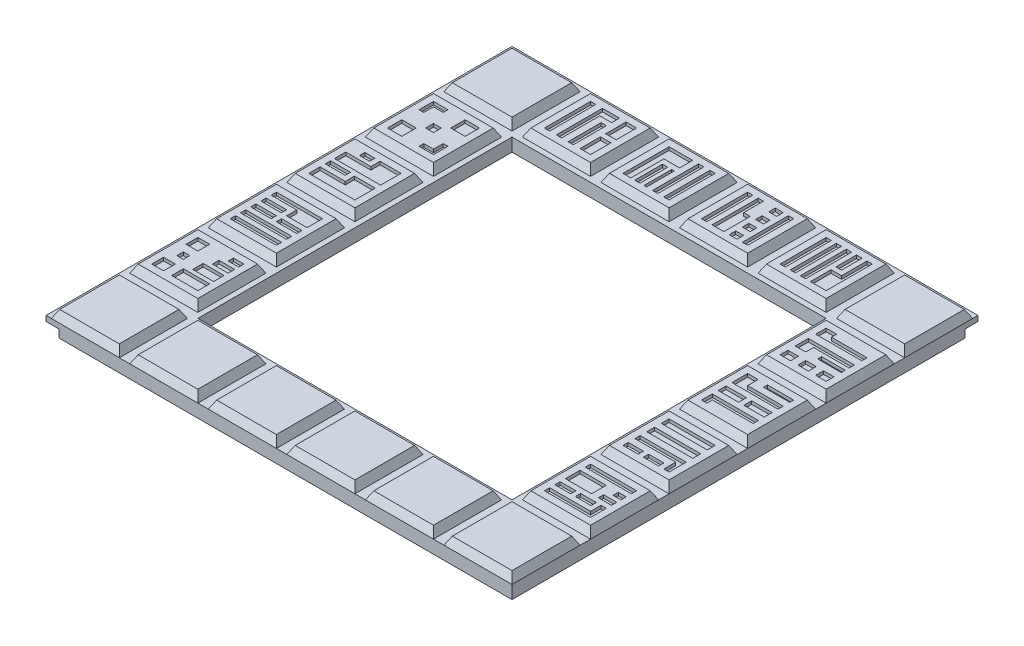
SolidWorks part; units mm, degrees
ref_plane "Front Plane" through (0, 0, 0) normal (0, 0, 1) x (1, 0, 0)
ref_plane "Top Plane" through (0, 0, 0) normal (0, 1, 0) x (1, 0, 0)
ref_plane "Right Plane" through (0, 0, 0) normal (1, 0, 0) x (0, 0, -1)
sketch "Sketch1" plane through (0, 0, 0) normal (0, 1, 0) x (1, 0, 0)
  line L1 (0, 0) -> (-180, 0)
  line L2 (0, 0) -> (0, 180)
  line L3 (0, 180) -> (-180, 180)
  line L4 (-180, 0) -> (-180, 180)
  dimension "D1" = 180
  dimension "D2" = 180
extrude "Boss-Extrude1" add sketch "Sketch1" along normal blind 5
sketch "Sketch2" plane through (0, 5, 0) normal (0, 1, 0) x (1, 0, 0)
  line L0 (-180, 180) -> (-180, 0) construction
  line L1 (-150, 150) -> (-30, 150)
  line L2 (-150, 150) -> (-150, 30)
  line L3 (-150, 30) -> (-30, 30)
  line L4 (-30, 150) -> (-30, 30)
  line L5 (0, 180) -> (-180, 180) construction
  dimension "D1" = 120
  dimension "D2" = 120
  dimension "D3" = 30
  dimension "D4" = 30
extrude "Cut-Extrude1" cut sketch "Sketch2" against normal through all
sketch "Sketch3" plane through (0, 5, 0) normal (0, 1, 0) x (1, 0, 0)
  line L0 (-180, 180) -> (-180, 0) construction
  line L1 (-178, 178) -> (-152, 178)
  line L2 (-178, 178) -> (-178, 152)
  line L3 (-178, 152) -> (-152, 152)
  line L4 (-152, 178) -> (-152, 152)
  line L5 (-148, 152) -> (-122, 152)
  line L6 (-148, 152) -> (-148, 178)
  line L7 (-148, 178) -> (-122, 178)
  line L8 (-122, 152) -> (-122, 178)
  line L9 (-118, 178) -> (-92, 178)
  line L10 (-118, 178) -> (-118, 152)
  line L11 (-118, 152) -> (-92, 152)
  line L12 (-92, 178) -> (-92, 152)
  line L13 (-88, 152) -> (-62, 152)
  line L14 (-88, 152) -> (-88, 178)
  line L15 (-88, 178) -> (-62, 178)
  line L16 (-62, 152) -> (-62, 178)
  line L17 (-58, 178) -> (-32, 178)
  line L18 (-58, 178) -> (-58, 152)
  line L19 (-58, 152) -> (-32, 152)
  line L20 (-32, 178) -> (-32, 152)
  line L21 (-28, 152) -> (-2, 152)
  line L22 (-28, 152) -> (-28, 178)
  line L23 (-28, 178) -> (-2, 178)
  line L24 (-2, 152) -> (-2, 178)
  line L25 (-28, 148) -> (-2, 148)
  line L26 (-28, 148) -> (-28, 122)
  line L27 (-28, 122) -> (-2, 122)
  line L28 (-2, 148) -> (-2, 122)
  line L29 (-2, 118) -> (-28, 118)
  line L30 (-2, 118) -> (-2, 92)
  line L31 (-2, 92) -> (-28, 92)
  line L32 (-28, 118) -> (-28, 92)
  line L33 (-28, 88) -> (-2, 88)
  line L34 (-28, 88) -> (-28, 62)
  line L35 (-28, 62) -> (-2, 62)
  line L36 (-2, 88) -> (-2, 62)
  line L37 (-28, 58) -> (-2, 58)
  line L38 (-28, 58) -> (-28, 32)
  line L39 (-28, 32) -> (-2, 32)
  line L40 (-2, 58) -> (-2, 32)
  line L41 (-28, 28) -> (-2, 28)
  line L42 (-28, 28) -> (-28, 2)
  line L43 (-28, 2) -> (-2, 2)
  line L44 (-2, 28) -> (-2, 2)
  line L45 (-32, 28) -> (-58, 28)
  line L46 (-32, 28) -> (-32, 2)
  line L47 (-32, 2) -> (-58, 2)
  line L48 (-58, 28) -> (-58, 2)
  line L49 (-62, 28) -> (-88, 28)
  line L50 (-62, 28) -> (-62, 2)
  line L51 (-62, 2) -> (-88, 2)
  line L52 (-88, 28) -> (-88, 2)
  line L53 (-92, 28) -> (-118, 28)
  line L54 (-92, 28) -> (-92, 2)
  line L55 (-92, 2) -> (-118, 2)
  line L56 (-118, 28) -> (-118, 2)
  line L57 (-122, 28) -> (-148, 28)
  line L58 (-122, 28) -> (-122, 2)
  line L59 (-122, 2) -> (-148, 2)
  line L60 (-148, 28) -> (-148, 2)
  line L61 (-152, 28) -> (-178, 28)
  line L62 (-152, 28) -> (-152, 2)
  line L63 (-152, 2) -> (-178, 2)
  line L64 (-178, 28) -> (-178, 2)
  line L65 (-178, 32) -> (-152, 32)
  line L66 (-178, 32) -> (-178, 58)
  line L67 (-178, 58) -> (-152, 58)
  line L68 (-152, 32) -> (-152, 58)
  line L69 (-178, 62) -> (-152, 62)
  line L70 (-178, 62) -> (-178, 88)
  line L71 (-178, 88) -> (-152, 88)
  line L72 (-152, 62) -> (-152, 88)
  line L73 (-178, 92) -> (-152, 92)
  line L74 (-178, 92) -> (-178, 118)
  line L75 (-178, 118) -> (-152, 118)
  line L76 (-152, 92) -> (-152, 118)
  line L77 (-178, 122) -> (-152, 122)
  line L78 (-178, 122) -> (-178, 148)
  line L79 (-178, 148) -> (-152, 148)
  line L80 (-152, 122) -> (-152, 148)
  line L81 (0, 180) -> (-180, 180) construction
  line L82 (-180, 0) -> (0, 0) construction
  line L83 (0, 0) -> (0, 180) construction
  dimension "D1" = 26
  dimension "D2" = 2
  dimension "D3" = 2
  dimension "D4" = 4
  dimension "D5" = 2
  dimension "D6" = 4
  dimension "D7" = 4
  dimension "D8" = 4
  dimension "D9" = 4
  dimension "D10" = 4
  dimension "D11" = 2
  dimension "D12" = 4
  dimension "D13" = 4
extrude "Boss-Extrude2" add sketch "Sketch3" along normal blind 3
chamfer "Chamfer1" distance 3 distance2 1.6 80 edges at (-15, 8, -178) (-2, 8, -165) (-15, 8, -152) (-28, 8, -165) (-105, 8, -2) (-118, 8, -15) (-105, 8, -28) (-92, 8, -15) (-135, 8, -2) (-148, 8, -15) (-135, 8, -28) (-122, 8, -15) (-165, 8, -2) (-178, 8, -15) (-165, 8, -28) (-152, 8, -15) (-165, 8, -58) (-152, 8, -45) (-165, 8, -32) (-178, 8, -45) (-165, 8, -88) (-152, 8, -75) (-165, 8, -62) (-178, 8, -75) (-165, 8, -118) (-152, 8, -105) (-165, 8, -92) (-178, 8, -105) (-15, 8, -58) (-2, 8, -45) (-15, 8, -32) (-28, 8, -45) (-75, 8, -2) (-88, 8, -15) (-75, 8, -28) (-62, 8, -15) (-45, 8, -2) (-58, 8, -15) (-45, 8, -28) (-32, 8, -15) (-15, 8, -28) (-2, 8, -15) (-15, 8, -2) (-28, 8, -15) (-15, 8, -88) (-2, 8, -75) (-15, 8, -62) (-28, 8, -75) (-15, 8, -92) (-28, 8, -105) (-15, 8, -118) (-2, 8, -105) (-15, 8, -148) (-2, 8, -135) (-15, 8, -122) (-28, 8, -135) (-75, 8, -178) (-62, 8, -165) (-75, 8, -152) (-88, 8, -165) (-105, 8, -178) (-92, 8, -165) (-105, 8, -152) (-118, 8, -165) (-135, 8, -178) (-122, 8, -165) (-135, 8, -152) (-148, 8, -165) (-165, 8, -148) (-152, 8, -135) (-165, 8, -122) (-178, 8, -135) (-165, 8, -178) (-152, 8, -165) (-165, 8, -152) (-178, 8, -165) (-45, 8, -178) (-32, 8, -165) (-45, 8, -152) (-58, 8, -165)
sketch "Sketch4" plane through (0, 8, 0) normal (0, 1, 0) x (1, 0, 0)
  line L0 (-123.6, 176.4) -> (-146.4, 176.4) construction
  line L1 (-143.8, 173.8) -> (-141.8, 173.8)
  line L2 (-143.8, 173.8) -> (-143.8, 156.2)
  line L3 (-143.8, 156.2) -> (-141.8, 156.2)
  line L4 (-141.8, 173.8) -> (-141.8, 156.2)
  line L5 (-139.25, 156.2) -> (-137.25, 156.2)
  line L6 (-139.25, 156.2) -> (-139.25, 173.8)
  line L7 (-139.25, 173.8) -> (-137.25, 173.8)
  line L8 (-137.25, 156.2) -> (-137.25, 173.8)
  line L9 (-137.25, 173.8) -> (-132.75, 173.8)
  line L10 (-146.4, 153.6) -> (-123.6, 153.6) construction
  line L11 (-137.25, 170.8) -> (-132.75, 170.8)
  line L12 (-132.75, 173.8) -> (-132.75, 170.8)
  line L13 (-132.75, 168.8) -> (-134.75, 168.8)
  line L14 (-132.75, 168.8) -> (-132.75, 156.2)
  line L15 (-132.75, 156.2) -> (-134.75, 156.2)
  line L16 (-134.75, 168.8) -> (-134.75, 156.2)
  line L17 (-130.2, 156.2) -> (-126.2, 156.2)
  line L18 (-130.2, 156.2) -> (-130.2, 164)
  line L19 (-130.2, 164) -> (-126.2, 164)
  line L20 (-126.2, 156.2) -> (-126.2, 164)
  line L21 (-130.2, 166) -> (-126.2, 166)
  line L22 (-130.2, 166) -> (-130.2, 173.8)
  line L23 (-130.2, 173.8) -> (-126.2, 173.8)
  line L24 (-126.2, 166) -> (-126.2, 173.8)
  line L25 (-113.8, 156.2) -> (-110.8, 156.2)
  line L26 (-113.8, 156.2) -> (-113.8, 173.8)
  line L27 (-113.8, 173.8) -> (-110.8, 173.8)
  line L28 (-110.8, 156.2) -> (-110.8, 173.8)
  line L29 (-110.8, 168.8) -> (-104.8, 168.8)
  line L30 (-146.4, 176.4) -> (-146.4, 153.6) construction
  line L31 (-110.8, 173.8) -> (-104.8, 173.8)
  line L32 (-104.8, 168.8) -> (-104.8, 173.8)
  line L33 (-109.3, 166.8) -> (-107.3, 166.8)
  line L34 (-109.3, 166.8) -> (-109.3, 156.2)
  line L35 (-109.3, 156.2) -> (-107.3, 156.2)
  line L36 (-107.3, 166.8) -> (-107.3, 156.2)
  line L37 (-105.8, 156.2) -> (-104.8, 156.2)
  line L38 (-105.8, 156.2) -> (-105.8, 166.8)
  line L39 (-105.8, 166.8) -> (-104.8, 166.8)
  line L40 (-104.8, 156.2) -> (-104.8, 166.8)
  line L41 (-102.5, 173.8) -> (-100.5, 173.8)
  line L42 (-102.5, 173.8) -> (-102.5, 156.2)
  line L43 (-102.5, 156.2) -> (-100.5, 156.2)
  line L44 (-100.5, 173.8) -> (-100.5, 156.2)
  line L45 (-98.2, 156.2) -> (-96.2, 156.2)
  line L46 (-98.2, 156.2) -> (-98.2, 173.8)
  line L47 (-98.2, 173.8) -> (-96.2, 173.8)
  line L48 (-96.2, 156.2) -> (-96.2, 173.8)
  line L49 (-83.8, 173.8) -> (-81.8, 173.8)
  line L50 (-83.8, 173.8) -> (-83.8, 156.2)
  line L51 (-83.8, 156.2) -> (-81.8, 156.2)
  line L52 (-81.8, 173.8) -> (-81.8, 156.2)
  line L53 (-79.7667, 156.2) -> (-77.7667, 156.2)
  line L54 (-79.7667, 156.2) -> (-79.7667, 173.8)
  line L55 (-79.7667, 173.8) -> (-77.7667, 173.8)
  line L56 (-77.7667, 156.2) -> (-77.7667, 173.8)
  line L57 (-77.7667, 166.2667) -> (-75.2667, 166.2667)
  line L58 (-123.6, 153.6) -> (-123.6, 176.4) construction
  line L59 (-77.7667, 156.2) -> (-75.2667, 156.2)
  line L60 (-75.2667, 166.2667) -> (-75.2667, 156.2)
  line L61 (-73.2333, 156.2) -> (-70.2333, 156.2)
  line L62 (-73.2333, 156.2) -> (-73.2333, 158.7)
  line L63 (-73.2333, 158.7) -> (-70.2333, 158.7)
  line L64 (-70.2333, 156.2) -> (-70.2333, 158.7)
  line L65 (-73.2333, 161.2333) -> (-70.2333, 161.2333)
  line L66 (-73.2333, 161.2333) -> (-73.2333, 163.7333)
  line L67 (-73.2333, 163.7333) -> (-70.2333, 163.7333)
  line L68 (-70.2333, 161.2333) -> (-70.2333, 163.7333)
  line L69 (-73.2333, 166.2667) -> (-70.2333, 166.2667)
  line L70 (-73.2333, 166.2667) -> (-73.2333, 168.7667)
  line L71 (-73.2333, 168.7667) -> (-70.2333, 168.7667)
  line L72 (-70.2333, 166.2667) -> (-70.2333, 168.7667)
  line L73 (-73.2333, 171.3) -> (-70.2333, 171.3)
  line L74 (-73.2333, 171.3) -> (-73.2333, 173.8)
  line L75 (-73.2333, 173.8) -> (-70.2333, 173.8)
  line L76 (-70.2333, 171.3) -> (-70.2333, 173.8)
  line L77 (-68.2, 173.8) -> (-66.2, 173.8)
  line L78 (-68.2, 173.8) -> (-68.2, 156.2)
  line L79 (-68.2, 156.2) -> (-66.2, 156.2)
  line L80 (-66.2, 173.8) -> (-66.2, 156.2)
  line L81 (-53.8, 173.8) -> (-51.8, 173.8)
  line L82 (-53.8, 173.8) -> (-53.8, 156.2)
  line L83 (-53.8, 156.2) -> (-51.8, 156.2)
  line L84 (-51.8, 173.8) -> (-51.8, 156.2)
  line L85 (-49.9333, 156.2) -> (-47.9333, 156.2)
  line L86 (-49.9333, 156.2) -> (-49.9333, 173.8)
  line L87 (-49.9333, 173.8) -> (-47.9333, 173.8)
  line L88 (-47.9333, 156.2) -> (-47.9333, 173.8)
  line L89 (-46.0667, 173.8) -> (-44.0667, 173.8)
  line L90 (-46.0667, 173.8) -> (-46.0667, 156.2)
  line L91 (-46.0667, 156.2) -> (-44.0667, 156.2)
  line L92 (-44.0667, 173.8) -> (-44.0667, 156.2)
  line L93 (-42.2, 173.8) -> (-40.0667, 173.8)
  line L94 (-42.2, 173.8) -> (-42.2, 165.9333)
  line L95 (-42.2, 165.9333) -> (-40.0667, 165.9333)
  line L96 (-40.0667, 173.8) -> (-40.0667, 165.9333)
  line L97 (-38.2, 173.8) -> (-36.2, 173.8)
  line L98 (-38.2, 173.8) -> (-38.2, 156.2)
  line L99 (-38.2, 156.2) -> (-36.2, 156.2)
  line L100 (-36.2, 173.8) -> (-36.2, 156.2)
  line L101 (-42.2, 156.2) -> (-38.2, 156.2)
  line L102 (-42.2, 156.2) -> (-42.2, 164.0667)
  line L103 (-42.2, 164.0667) -> (-38.2, 164.0667)
  line L104 (-93.6, 153.6) -> (-93.6, 176.4) construction
  line L105 (-116.4, 176.4) -> (-116.4, 153.6) construction
  line L106 (-63.6, 153.6) -> (-63.6, 176.4) construction
  line L107 (-86.4, 176.4) -> (-86.4, 153.6) construction
  line L108 (-56.4, 176.4) -> (-56.4, 153.6) construction
  line L109 (-33.6, 153.6) -> (-33.6, 176.4) construction
  line L110 (-70.2333, 171.3) -> (-70.2333, 168.7667) construction
  line L111 (-70.2333, 166.2667) -> (-70.2333, 163.7333) construction
  line L112 (-70.2333, 161.2333) -> (-70.2333, 158.7) construction
  line L113 (-141.8, 156.2) -> (-139.25, 156.2) construction
  line L114 (-132.75, 156.2) -> (-130.2, 156.2) construction
  line L115 (-104.8, 156.2) -> (-102.5, 156.2) construction
  line L116 (-100.5, 156.2) -> (-98.2, 156.2) construction
  line L117 (-51.8, 156.2) -> (-49.9333, 156.2) construction
  line L118 (-47.9333, 156.2) -> (-46.0667, 156.2) construction
  line L119 (-44.0667, 156.2) -> (-42.2, 156.2) construction
  line L120 (-42.2, 164.0667) -> (-42.2, 165.9333) construction
  line L121 (-40.0667, 173.8) -> (-38.2, 173.8) construction
  line L122 (-81.8, 156.2) -> (-79.7667, 156.2) construction
  line L123 (-75.2667, 156.2) -> (-73.2333, 156.2) construction
  line L124 (-70.2333, 156.2) -> (-68.2, 156.2) construction
  point P120 (-127.7927, 145.733)
  dimension "D1" = 2.6
  dimension "D2" = 2.6
  dimension "D3" = 2.6
  dimension "D4" = 2.6
  dimension "D5" = 2.6
  dimension "D6" = 2
  dimension "D7" = 2
  dimension "D8" = 2
  dimension "D9" = 1
  dimension "D10" = 2
  dimension "D11" = 2
  dimension "D12" = 2.6
  dimension "D13" = 2.6
  dimension "D14" = 2.6
  dimension "D15" = 2.6
  dimension "D16" = 2
  dimension "D17" = 2
  dimension "D18" = 2.5
  dimension "D19" = 2
  dimension "D21" = 3
  dimension "D23" = 2.6
  dimension "D24" = 2.6
  dimension "D25" = 2
  dimension "D26" = 2.5
  dimension "D27" = 2
  dimension "D28" = 3
  dimension "D29" = 2
  dimension "D30" = 2
  dimension "D31" = 4
  dimension "D32" = 4
  dimension "D33" = 3
  dimension "D34" = 6
  dimension "D35" = 1.5
  dimension "D36" = 5
  dimension "D37" = 2
  dimension "D38" = 2
  dimension "D39" = 2
  dimension "D40" = 2.5
  dimension "D41" = 2
  dimension "D42" = 2
  dimension "D43" = 4
extrude "Motifs_Ligne_1" cut sketch "Sketch4" against normal blind 1.2 contours L13 L16 L15 L14 | L12 L9 L8 L11 | L17 L20 L19 L18 | L21 L24 L23 L22 | L5 L8 L7 L6 | L25 L28 L27 L26 | L29 L32 L31 L28 | L36 L33 L34 L35 | L37 L40 L39 L38 | L44 L41 L42 L43 | L45 L48 L47 L46 | L103 L102 L101 L98 | L100 L97 L98 L99 | L96 L93 L94 L95 | L92 L89 L90 L91 | L85 L88 L87 L86 | L84 L81 L82 L83 | L73 L76 L75 L74 | L53 L56 L55 L54 | L60 L57 L56 L59 | L52 L49 L50 L51 | L65 L68 L67 L66 | L61 L64 L63 L62 | L69 L72 L71 L70 | L80 L77 L78 L79 | L2 L3 L4 L1
sketch "Sketch5" plane through (0, 0, 0) normal (0, -1, 0) x (1, 0, 0)
  line L0 (0, -175) -> (0, -180)
  line L1 (-180, -180) -> (-180, 0)
  line L2 (-180, 0) -> (-175, 0)
  line L4 (-175, -175) -> (0, -175)
  line L5 (0, -180) -> (-180, -180)
  line L6 (-175, 0) -> (-175, -175)
  line L7 (-180, 0) -> (0, 0) construction
  dimension "D1" = 5
  dimension "D2" = 5
  dimension "D3" = 0
  dimension "D4" = 0
extrude "Cut-Extrude3" cut sketch "Sketch5" against normal blind 3
sketch "Sketch6" plane through (0, 0, 0) normal (0, -1, 0) x (1, 0, 0)
  line L0 (0, 0) -> (0, -194.7494)
  line L1 (0, -194.7494) -> (-2, -194.7494)
  line L2 (-2, -194.7494) -> (-2, -2)
  line L3 (-2, -2) -> (-190.0347, -2)
  line L4 (-190.0347, -2) -> (-190.0347, 0)
  line L5 (-190.0347, 0) -> (0, 0)
  dimension "D1" = 2
  dimension "D2" = 2
extrude "Cut-Extrude4" cut sketch "Sketch6" against normal through all
sketch "Sketch7" plane through (0, 8, 0) normal (0, 1, 0) x (1, 0, 0)
  line L0 (-173.8, 146.4) -> (-173.8, 33.6) construction
  line L1 (-153.6, 146.4) -> (-176.4, 146.4) construction
  line L2 (-176.4, 33.6) -> (-153.6, 33.6) construction
  line L3 (-156.2, 146.4) -> (-156.2, 33.6) construction
  line L4 (-176.4, 36.2) -> (-153.6, 36.2) construction
  line L5 (-176.4, 56.4) -> (-176.4, 33.6) construction
  line L6 (-153.6, 33.6) -> (-153.6, 56.4) construction
  line L7 (-176.4, 143.8) -> (-153.6, 143.8) construction
  line L8 (-176.4, 146.4) -> (-176.4, 123.6) construction
  line L9 (-153.6, 123.6) -> (-153.6, 146.4) construction
  line L10 (-176.4, 126.2) -> (-153.6, 126.2) construction
  line L11 (-176.4, 96.2) -> (-153.6, 96.2) construction
  line L12 (-176.4, 116.4) -> (-176.4, 93.6) construction
  line L13 (-153.6, 93.6) -> (-153.6, 116.4) construction
  line L14 (-176.4, 113.8) -> (-153.6, 113.8) construction
  line L15 (-176.4, 83.8) -> (-153.6, 83.8) construction
  line L16 (-176.4, 86.4) -> (-176.4, 63.6) construction
  line L17 (-153.6, 63.6) -> (-153.6, 86.4) construction
  line L18 (-153.6, 66.2) -> (-176.4, 66.2) construction
  line L19 (-176.4, 53.8) -> (-153.6, 53.8) construction
  line L20 (-176.4, 123.6) -> (-153.6, 123.6) construction
  line L21 (-153.6, 116.4) -> (-176.4, 116.4) construction
  line L22 (-176.4, 93.6) -> (-153.6, 93.6) construction
  line L23 (-153.6, 86.4) -> (-176.4, 86.4) construction
  line L24 (-176.4, 63.6) -> (-153.6, 63.6) construction
  line L25 (-153.6, 56.4) -> (-176.4, 56.4) construction
  line L26 (-173.8, 138.3) -> (-172, 138.3)
  line L27 (-173.8, 126.2) -> (-168.3, 126.2)
  line L28 (-173.8, 126.2) -> (-173.8, 131.7)
  line L29 (-173.8, 131.7) -> (-168.3, 131.7)
  line L30 (-168.3, 126.2) -> (-168.3, 131.7)
  line L31 (-166.5, 133.5) -> (-163.5, 133.5)
  line L32 (-166.5, 133.5) -> (-166.5, 136.5)
  line L33 (-166.5, 136.5) -> (-163.5, 136.5)
  line L34 (-163.5, 133.5) -> (-163.5, 136.5)
  line L35 (-156.2, 143.8) -> (-161.7, 143.8)
  line L36 (-156.2, 143.8) -> (-156.2, 138.3)
  line L37 (-156.2, 138.3) -> (-161.7, 138.3)
  line L38 (-161.7, 143.8) -> (-161.7, 138.3)
  line L39 (-172, 138.3) -> (-172, 142)
  line L40 (-172, 142) -> (-168.3, 142)
  line L41 (-168.3, 142) -> (-168.3, 143.8)
  line L42 (-168.3, 143.8) -> (-173.8, 143.8)
  line L43 (-173.8, 143.8) -> (-173.8, 138.3)
  line L44 (-161.7, 126.2) -> (-156.2, 126.2)
  line L45 (-156.2, 126.2) -> (-156.2, 131.7)
  line L46 (-156.2, 131.7) -> (-158, 131.7)
  line L47 (-158, 131.7) -> (-158, 128)
  line L48 (-158, 128) -> (-161.7, 128)
  line L49 (-161.7, 126.2) -> (-161.7, 128)
  line L50 (-173.8, 131.7) -> (-173.8, 138.3) construction
  line L51 (-168.3, 143.8) -> (-161.7, 143.8) construction
  line L52 (-168.3, 126.2) -> (-161.7, 126.2) construction
  line L53 (-156.2, 131.7) -> (-156.2, 138.3) construction
  line L54 (-172, 138.3) -> (-172, 131.7) construction
  line L55 (-166.5, 133.5) -> (-173.8, 133.5) construction
  line L56 (-166.5, 133.5) -> (-166.5, 126.2) construction
  line L57 (-163.5, 136.5) -> (-163.5, 143.8) construction
  line L58 (-163.5, 136.5) -> (-156.2, 136.5) construction
  line L59 (-173.8, 106) -> (-156.2, 106)
  line L60 (-156.2, 106) -> (-156.2, 113.8)
  line L61 (-156.2, 113.8) -> (-164.2, 113.8)
  line L62 (-164.2, 113.8) -> (-164.2, 110.3)
  line L63 (-164.2, 110.3) -> (-173.8, 110.3)
  line L64 (-173.8, 110.3) -> (-173.8, 106)
  line L65 (-173.8, 96.2) -> (-173.8, 100.5)
  line L66 (-173.8, 100.5) -> (-164.2, 100.5)
  line L67 (-164.2, 100.5) -> (-164.2, 104)
  line L68 (-164.2, 104) -> (-156.2, 104)
  line L69 (-156.2, 104) -> (-156.2, 96.2)
  line L70 (-156.2, 96.2) -> (-173.8, 96.2)
  line L71 (-173.8, 83.8) -> (-156.2, 83.8)
  line L72 (-173.8, 104.5) -> (-166.2, 104.5)
  line L73 (-173.8, 104.5) -> (-173.8, 102.5)
  line L74 (-173.8, 102.5) -> (-166.2, 102.5)
  line L75 (-166.2, 104.5) -> (-166.2, 102.5)
  line L76 (-170, 113.8) -> (-166.2, 113.8)
  line L77 (-170, 113.8) -> (-170, 111.8)
  line L78 (-170, 111.8) -> (-166.2, 111.8)
  line L79 (-166.2, 113.8) -> (-166.2, 111.8)
  line L80 (-173.8, 66.2) -> (-156.2, 66.2)
  line L81 (-173.8, 66.2) -> (-173.8, 68.2)
  line L82 (-173.8, 68.2) -> (-156.2, 68.2)
  line L83 (-156.2, 66.2) -> (-156.2, 68.2)
  line L84 (-156.2, 70.1) -> (-173.8, 70.1)
  line L85 (-156.2, 70.1) -> (-156.2, 72.1)
  line L86 (-156.2, 72.1) -> (-173.8, 72.1)
  line L87 (-173.8, 70.1) -> (-173.8, 72.1)
  line L88 (-173.8, 74) -> (-166, 74)
  line L89 (-173.8, 74) -> (-173.8, 76)
  line L90 (-173.8, 76) -> (-166, 76)
  line L91 (-166, 74) -> (-166, 76)
  line L92 (-164, 76) -> (-156.2, 76)
  line L93 (-164, 76) -> (-164, 74)
  line L94 (-164, 74) -> (-156.2, 74)
  line L95 (-156.2, 76) -> (-156.2, 74)
  line L96 (-173.8, 77.9) -> (-166, 77.9)
  line L97 (-173.8, 77.9) -> (-173.8, 79.9)
  line L98 (-173.8, 79.9) -> (-166, 79.9)
  line L99 (-166, 77.9) -> (-166, 79.9)
  line L100 (-156.2, 83.8) -> (-156.2, 77.9)
  line L101 (-156.2, 77.9) -> (-164, 77.9)
  line L102 (-164, 77.9) -> (-164, 81.8)
  line L103 (-164, 81.8) -> (-173.8, 81.8)
  line L104 (-173.8, 81.8) -> (-173.8, 83.8)
  line L105 (-173.8, 68.2) -> (-173.8, 70.1) construction
  line L106 (-173.8, 72.1) -> (-173.8, 74) construction
  line L107 (-166, 79.9) -> (-166, 81.8) construction
  line L108 (-166, 77.9) -> (-166, 76) construction
  line L109 (-166, 74) -> (-166, 72.1) construction
  line L110 (-166, 70.1) -> (-166, 68.2) construction
  line L111 (-159.5704, 40.7) -> (-159.5704, 42.2333) construction
  line L112 (-173.8, 53.8) -> (-169.3, 53.8)
  line L113 (-173.8, 53.8) -> (-173.8, 49.3)
  line L114 (-173.8, 49.3) -> (-169.3, 49.3)
  line L115 (-169.3, 53.8) -> (-169.3, 49.3)
  line L116 (-173.8, 36.2) -> (-169.3, 36.2)
  line L117 (-173.8, 36.2) -> (-173.8, 40.7)
  line L118 (-173.8, 40.7) -> (-169.3, 40.7)
  line L119 (-169.3, 36.2) -> (-169.3, 40.7)
  line L120 (-169.3, 43.75) -> (-171.8, 43.75)
  line L121 (-169.3, 43.75) -> (-169.3, 46.25)
  line L122 (-169.3, 46.25) -> (-171.8, 46.25)
  line L123 (-171.8, 43.75) -> (-171.8, 46.25)
  line L124 (-156.2, 53.8) -> (-160.2, 53.8)
  line L125 (-156.2, 53.8) -> (-156.2, 51.8)
  line L126 (-156.2, 51.8) -> (-160.2, 51.8)
  line L127 (-160.2, 53.8) -> (-160.2, 51.8)
  line L128 (-156.2, 50.2667) -> (-162.2, 50.2667)
  line L129 (-156.2, 50.2667) -> (-156.2, 47.7667)
  line L130 (-156.2, 47.7667) -> (-162.2, 47.7667)
  line L131 (-162.2, 50.2667) -> (-162.2, 47.7667)
  line L132 (-156.2, 46.2333) -> (-164.2, 46.2333)
  line L133 (-156.2, 46.2333) -> (-156.2, 42.2333)
  line L134 (-156.2, 42.2333) -> (-164.2, 42.2333)
  line L135 (-164.2, 46.2333) -> (-164.2, 42.2333)
  line L136 (-156.2, 40.7) -> (-166.2, 40.7)
  line L137 (-156.2, 40.7) -> (-156.2, 36.2)
  line L138 (-156.2, 36.2) -> (-166.2, 36.2)
  line L139 (-166.2, 40.7) -> (-166.2, 36.2)
  line L140 (-159.5704, 46.2333) -> (-159.5704, 47.7667) construction
  line L141 (-159.5704, 50.2667) -> (-159.5704, 51.8) construction
  line L142 (-169.3, 46.25) -> (-169.3, 49.3) construction
  line L143 (-169.3, 43.75) -> (-169.3, 40.7) construction
  dimension "D1" = 2.6
  dimension "D2" = 2.6
  dimension "D3" = 2.6
  dimension "D4" = 2.6
  dimension "D5" = 2.6
  dimension "D6" = 2.6
  dimension "D7" = 2.6
  dimension "D8" = 2.6
  dimension "D9" = 2.6
  dimension "D10" = 2.6
  dimension "D11" = 1.8
  dimension "D12" = 5.5
  dimension "D13" = 1.5
  dimension "D14" = 3
  dimension "D15" = 2
  dimension "D16" = 2
  dimension "D17" = 2
  dimension "D18" = 8
  dimension "D19" = 2
  dimension "D20" = 3.8
  dimension "D21" = 2
  dimension "D22" = 2
  dimension "D23" = 2
  dimension "D24" = 2.5
  dimension "D25" = 4
  dimension "D26" = 4.5
  dimension "D27" = 10
  dimension "D28" = 8
  dimension "D29" = 6
  dimension "D30" = 4
  dimension "D31" = 2.5
  dimension "D32" = 4.5
extrude "Cut-Extrude5" cut sketch "Sketch7" against normal blind 1.2
sketch "Sketch8" plane through (0, 8, 0) normal (0, 1, 0) x (1, 0, 0)
  line L0 (-23.8, 38.2) -> (-23.8, 36.2)
  line L1 (-15.2, 133.5) -> (-6.2, 133.5)
  line L2 (-15.2, 133.5) -> (-15.2, 132)
  line L3 (-15.2, 132) -> (-6.2, 132)
  line L4 (-6.2, 133.5) -> (-6.2, 132)
  line L5 (-23.8, 129.2) -> (-19.8, 129.2)
  line L6 (-23.8, 129.2) -> (-23.8, 126.2)
  line L7 (-23.8, 126.2) -> (-19.8, 126.2)
  line L8 (-19.8, 129.2) -> (-19.8, 126.2)
  line L9 (-17, 129.2) -> (-13, 129.2)
  line L10 (-17, 129.2) -> (-17, 126.2)
  line L11 (-17, 126.2) -> (-13, 126.2)
  line L12 (-13, 129.2) -> (-13, 126.2)
  line L13 (-10.2, 129.2) -> (-6.2, 129.2)
  line L14 (-10.2, 129.2) -> (-10.2, 126.2)
  line L15 (-10.2, 126.2) -> (-6.2, 126.2)
  line L16 (-6.2, 129.2) -> (-6.2, 126.2)
  line L17 (-16.2, 113.8) -> (-6.2, 113.8)
  line L18 (-16.2, 113.8) -> (-16.2, 112.3)
  line L19 (-16.2, 112.3) -> (-6.2, 112.3)
  line L20 (-6.2, 113.8) -> (-6.2, 112.3)
  line L21 (-23.8, 105.5524) -> (-16, 105.5524)
  line L22 (-23.8, 105.5524) -> (-23.8, 102.5524)
  line L23 (-23.8, 102.5524) -> (-16, 102.5524)
  line L24 (-16, 105.5524) -> (-16, 102.5524)
  line L25 (-14, 105.5524) -> (-6.2, 105.5524)
  line L26 (-14, 105.5524) -> (-14, 102.5524)
  line L27 (-14, 102.5524) -> (-6.2, 102.5524)
  line L28 (-6.2, 105.5524) -> (-6.2, 102.5524)
  line L29 (-23.8, 83.8) -> (-6.2, 83.8)
  line L30 (-23.8, 83.8) -> (-23.8, 80.8)
  line L31 (-23.8, 80.8) -> (-6.2, 80.8)
  line L32 (-6.2, 83.8) -> (-6.2, 80.8)
  line L33 (-6.2, 78.2667) -> (-23.8, 78.2667)
  line L34 (-6.2, 78.2667) -> (-6.2, 75.2667)
  line L35 (-6.2, 75.2667) -> (-23.8, 75.2667)
  line L36 (-23.8, 78.2667) -> (-23.8, 75.2667)
  line L37 (-23.8, 68.2) -> (-18, 68.2)
  line L38 (-23.8, 68.2) -> (-23.8, 66.2)
  line L39 (-23.8, 66.2) -> (-18, 66.2)
  line L40 (-18, 68.2) -> (-18, 66.2)
  line L41 (-16, 68.2) -> (-10.2, 68.2)
  line L42 (-16, 68.2) -> (-16, 66.2)
  line L43 (-16, 66.2) -> (-10.2, 66.2)
  line L44 (-10.2, 68.2) -> (-10.2, 66.2)
  line L45 (-23.8, 53.8) -> (-6.2, 53.8)
  line L46 (-23.8, 53.8) -> (-23.8, 51.8)
  line L47 (-23.8, 51.8) -> (-6.2, 51.8)
  line L48 (-6.2, 53.8) -> (-6.2, 51.8)
  line L49 (-23.8, 49.8) -> (-13.8, 49.8)
  line L50 (-23.8, 49.8) -> (-23.8, 44.2)
  line L51 (-23.8, 44.2) -> (-13.8, 44.2)
  line L52 (-13.8, 49.8) -> (-13.8, 44.2)
  line L53 (-9.2, 49.8) -> (-6.2, 49.8)
  line L54 (-9.2, 49.8) -> (-9.2, 47.8)
  line L55 (-9.2, 47.8) -> (-6.2, 47.8)
  line L56 (-6.2, 49.8) -> (-6.2, 47.8)
  line L57 (-11.2, 46.2) -> (-6.2, 46.2)
  line L58 (-11.2, 46.2) -> (-11.2, 44.2)
  line L59 (-11.2, 44.2) -> (-6.2, 44.2)
  line L60 (-6.2, 46.2) -> (-6.2, 44.2)
  line L61 (-23.8, 42.2) -> (-17.8, 42.2)
  line L62 (-23.8, 42.2) -> (-23.8, 40.2)
  line L63 (-23.8, 40.2) -> (-17.8, 40.2)
  line L64 (-17.8, 42.2) -> (-17.8, 40.2)
  line L65 (-16, 42.2) -> (-10, 42.2)
  line L66 (-16, 42.2) -> (-16, 40.2)
  line L67 (-16, 40.2) -> (-10, 40.2)
  line L68 (-10, 42.2) -> (-10, 40.2)
  line L69 (-23.8, 36.2) -> (-6.2, 36.2)
  line L70 (-6.2, 36.2) -> (-6.2, 42.2)
  line L71 (-6.2, 42.2) -> (-8.2, 42.2)
  line L72 (-8.2, 42.2) -> (-8.2, 38.2)
  line L73 (-8.2, 38.2) -> (-23.8, 38.2)
  line L74 (-23.8, 70.7333) -> (-23.8, 72.7333)
  line L75 (-23.8, 72.7333) -> (-6.2, 72.7333)
  line L76 (-6.2, 72.7333) -> (-6.2, 66.2)
  line L77 (-6.2, 66.2) -> (-8.2, 66.2)
  line L78 (-8.2, 66.2) -> (-8.2, 70.7333)
  line L79 (-8.2, 70.7333) -> (-23.8, 70.7333)
  line L80 (-23.8, 96.2) -> (-23.8, 100.3049)
  line L81 (-23.8, 100.3049) -> (-6.2, 100.3049)
  line L82 (-6.2, 100.3049) -> (-6.2, 98.3049)
  line L83 (-6.2, 98.3049) -> (-21.8, 98.3049)
  line L84 (-21.8, 98.3049) -> (-21.8, 96.2)
  line L85 (-21.8, 96.2) -> (-23.8, 96.2)
  line L86 (-23.8, 113.8) -> (-23.8, 107.8)
  line L87 (-23.8, 107.8) -> (-6.2, 107.8)
  line L88 (-6.2, 107.8) -> (-6.2, 109.8)
  line L89 (-6.2, 109.8) -> (-19.8, 109.8)
  line L90 (-19.8, 109.8) -> (-19.8, 113.8)
  line L91 (-19.8, 113.8) -> (-23.8, 113.8)
  line L92 (-23.8, 132) -> (-19.8, 132)
  line L93 (-19.8, 132) -> (-19.8, 135)
  line L94 (-19.8, 135) -> (-6.2, 135)
  line L95 (-6.2, 135) -> (-6.2, 137)
  line L96 (-6.2, 137) -> (-23.8, 137)
  line L97 (-23.8, 137) -> (-23.8, 132)
  line L98 (-23.8, 143.8) -> (-23.8, 139.8)
  line L99 (-23.8, 139.8) -> (-6.2, 139.8)
  line L100 (-6.2, 139.8) -> (-6.2, 141.8)
  line L101 (-6.2, 141.8) -> (-19.8, 141.8)
  line L102 (-19.8, 141.8) -> (-19.8, 143.8)
  line L103 (-19.8, 143.8) -> (-23.8, 143.8)
  line L104 (-3.6, 33.6) -> (-3.6, 56.4) construction
  line L105 (-26.4, 146.4) -> (-26.4, 123.6) construction
  line L106 (-3.6, 146.4) -> (-26.4, 146.4) construction
  line L107 (-26.4, 123.6) -> (-3.6, 123.6) construction
  line L108 (-3.6, 116.4) -> (-26.4, 116.4) construction
  line L109 (-26.4, 93.6) -> (-3.6, 93.6) construction
  line L110 (-3.6, 86.4) -> (-26.4, 86.4) construction
  line L111 (-26.4, 63.6) -> (-3.6, 63.6) construction
  line L112 (-3.6, 56.4) -> (-26.4, 56.4) construction
  line L113 (-26.4, 33.6) -> (-3.6, 33.6) construction
  line L114 (-23.8, 68.2) -> (-23.8, 70.7333) construction
  line L115 (-23.8, 72.7333) -> (-23.8, 75.2667) construction
  line L116 (-23.8, 78.2667) -> (-23.8, 80.8) construction
  line L117 (-23.8, 38.2) -> (-23.8, 40.2) construction
  line L118 (-23.8, 42.2) -> (-23.8, 44.2) construction
  line L119 (-23.8, 49.8) -> (-23.8, 51.8) construction
  line L120 (-17.8, 42.2) -> (-16, 42.2) construction
  line L121 (-10, 42.2) -> (-8.2, 42.2) construction
  line L122 (-23.8, 100.3049) -> (-23.8, 102.5524) construction
  line L123 (-23.8, 105.5524) -> (-23.8, 107.8) construction
  line L124 (-23.8, 129.2) -> (-23.8, 132) construction
  line L125 (-23.8, 137) -> (-23.8, 139.8) construction
  line L126 (-19.8, 126.2) -> (-17, 126.2) construction
  line L127 (-13, 126.2) -> (-10.2, 126.2) construction
  dimension "D1" = 2.6
  dimension "D2" = 2.6
  dimension "D3" = 2.6
  dimension "D4" = 2.6
  dimension "D5" = 2.6
  dimension "D6" = 2.6
  dimension "D7" = 2.6
  dimension "D8" = 2.6
  dimension "D9" = 2.6
  dimension "D10" = 2.6
  dimension "D11" = 3
  dimension "D12" = 2
  dimension "D13" = 2
  dimension "D14" = 2
  dimension "D15" = 2
  dimension "D16" = 2
  dimension "D17" = 2
  dimension "D18" = 2
  dimension "D19" = 2
  dimension "D20" = 2
  dimension "D21" = 10
  dimension "D22" = 6
  dimension "D23" = 2
  dimension "D24" = 5
  dimension "D25" = 3
  dimension "D26" = 2
  dimension "D27" = 2
  dimension "D28" = 2
  dimension "D29" = 1.5
  dimension "D30" = 2
  dimension "D31" = 3
  dimension "D32" = 10
  dimension "D33" = 4
  dimension "D34" = 4.1049
  dimension "D35" = 6
  dimension "D36" = 2
  dimension "D37" = 4
  dimension "D38" = 4
  dimension "D39" = 4
  dimension "D40" = 5
  dimension "D41" = 2
  dimension "D42" = 3
  dimension "D43" = 4
  dimension "D44" = 9
  dimension "D45" = 1.5
extrude "Cut-Extrude6" cut sketch "Sketch8" against normal blind 1.2
